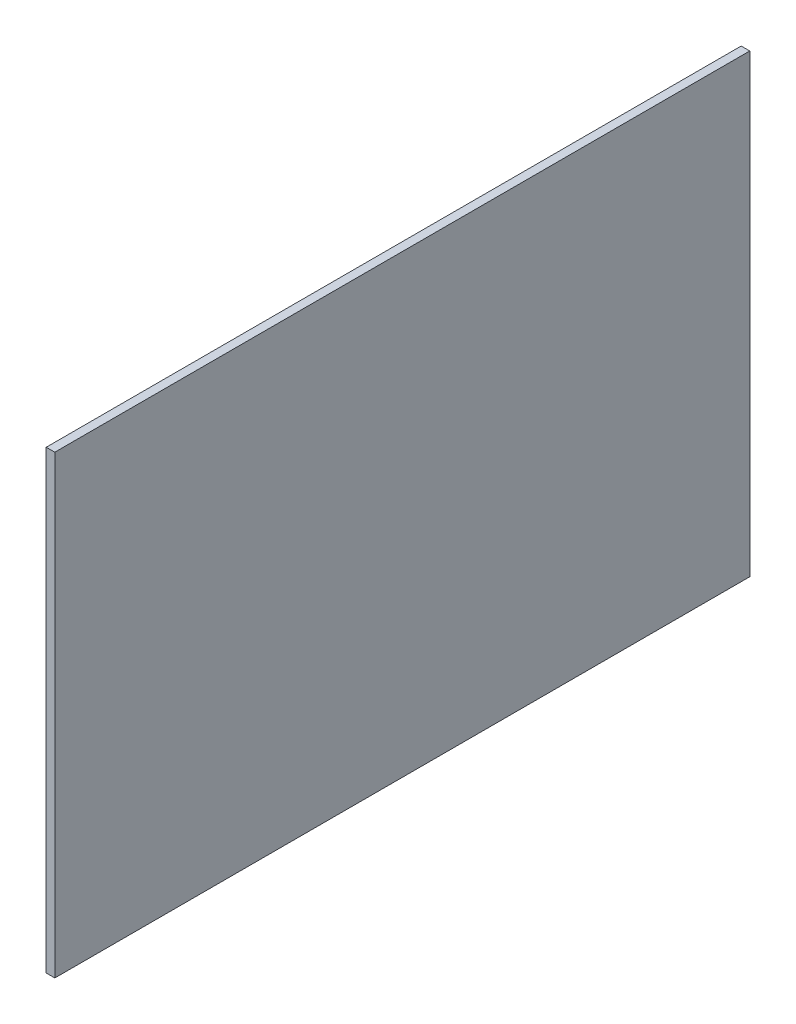
SolidWorks part; units mm, degrees
ref_plane "Front Plane" through (0, 0, 0) normal (0, 0, 1) x (1, 0, 0)
ref_plane "Top Plane" through (0, 0, 0) normal (0, 1, 0) x (1, 0, 0)
ref_plane "Right Plane" through (0, 0, 0) normal (1, 0, 0) x (0, 0, -1)
sketch "Sketch1" plane through (0, 0, 0) normal (0, 1, 0) x (1, 0, 0)
  line L2 (304, 55.73) -> (304, -749.2627)
  line L3 (304, -749.2627) -> (316.7, -749.2627)
  line L4 (316.7, 55.73) -> (316.7, -749.2627)
  line L6 (316.7, 55.73) -> (316.7, 279.5346)
  line L7 (316.7, 279.5346) -> (304, 279.5346)
  line L8 (304, 55.73) -> (304, 279.5346)
  dimension "D1" = 12.7
  dimension "D2" = 223.8046
  dimension "D3" = 804.9927
extrude "Boss-Extrude1" add sketch "Sketch1" along normal blind 674.1356
